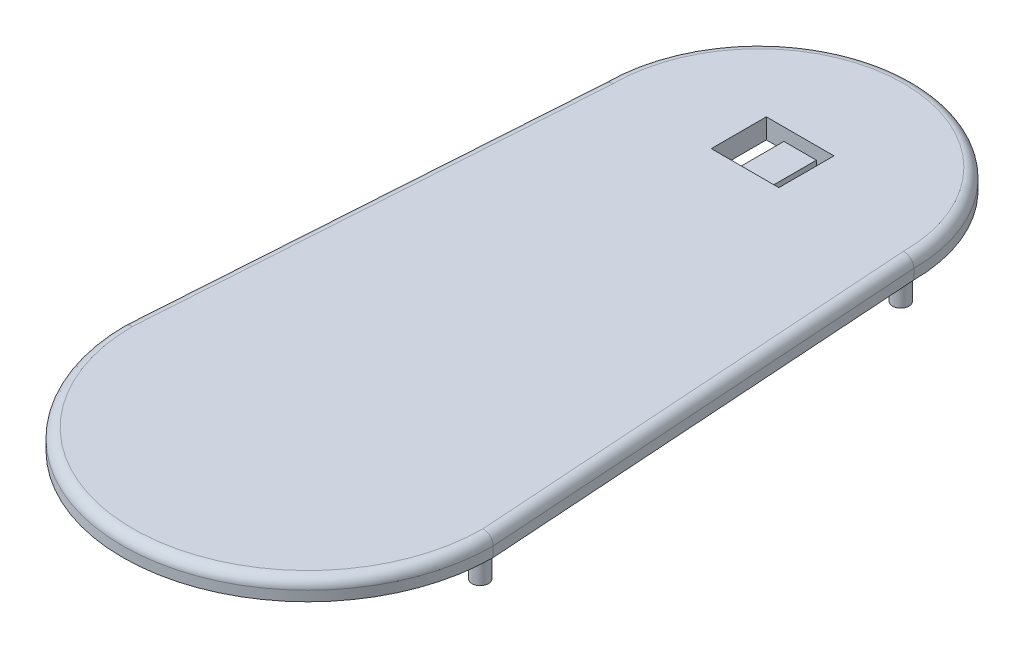
SolidWorks part; units mm, degrees
ref_plane "Front Plane" through (0, 0, 0) normal (0, 0, 1) x (1, 0, 0)
ref_plane "Top Plane" through (0, 0, 0) normal (0, 1, 0) x (1, 0, 0)
ref_plane "Right Plane" through (0, 0, 0) normal (1, 0, 0) x (0, 0, -1)
sketch "Sketch1" plane through (0, 0, 0) normal (0, 1, 0) x (1, 0, 0)
  line L0 (-31, 45) -> (-37, -45)
  line L1 (-31, 45) -> (31, 45)
  line L2 (-31, 45) -> (-31, -45)
  line L3 (-31, -45) -> (31, -45)
  line L4 (31, 45) -> (31, -45)
  line L5 (-31, 45) -> (31, -45) construction
  line L6 (-31, -45) -> (31, 45) construction
  line L7 (31, 45) -> (37, -45)
  circle A0 centre (0, 45) radius 31
  circle A1 centre (0, -45) radius 37
  point P0 (0, 0)
  dimension "D3" = 74
  dimension "D1" = 62
  dimension "D2" = 90
extrude "Boss-Extrude4" add sketch "Sketch1" along normal blind 4 contours L7 A1 L4 L3 L2 L0 | L4 A1 L2 L3 | A1 L4 A0 L2 | L1 A0 | L1 A0 | A1 L7 L4 | A1 L2 L0 region at (-32.823, 0, 5.2761) region at (0, 0, -58.1568) region at (0, 0, -4.2186) region at (0, 0, -31.8432) region at (0, 0, 59.0475) region at (32.823, 0, 5.2761) region at (0, 0, 28.6312)
sketch "Sketch8" plane through (0, 0, 0) normal (0, -1, 0) x (1, 0, 0)
  circle A0 centre (-34.4, 45) radius 1.65
  circle A1 centre (34.4, 45) radius 1.65
  circle A2 centre (28.4, -45) radius 1.65
  circle A3 centre (-28.4, -45) radius 1.65
  dimension "D1" = 3.3
  dimension "D3" = 3.3
  dimension "D5" = 3.3
  dimension "D7" = 3.3
  dimension "D2" = 2.6
  dimension "D4" = 2.6
  dimension "D6" = 2.6
  dimension "D8" = 2.6
extrude "Boss-Extrude5" add sketch "Sketch8" along normal blind 5
sketch "Sketch9" plane through (0, 4, 0) normal (0, 1, 0) x (1, 0, 0)
  line L1 (-7.9566, 54.5082) -> (5.5434, 54.5082)
  line L2 (-7.9566, 54.5082) -> (-7.9566, 43.5082)
  line L3 (-7.9566, 43.5082) -> (5.5434, 43.5082)
  line L4 (5.5434, 54.5082) -> (5.5434, 43.5082)
  line L5 (-7.9566, 54.5082) -> (5.5434, 43.5082) construction
  line L6 (-7.9566, 43.5082) -> (5.5434, 54.5082) construction
  point P0 (-1.2066, 49.0082)
  dimension "D1" = 13.5
  dimension "D2" = 11
extrude "Cut-Extrude3" cut sketch "Sketch9" against normal blind 2.5
sketch "Sketch10" plane through (0, 1.5, 0) normal (0, 1, 0) x (1, 0, 0)
  line L0 (-7.9566, 43.5082) -> (5.5434, 43.5082) construction
  line L1 (-7.9566, 54.5082) -> (-4.4566, 54.5082)
  line L2 (-7.9566, 54.5082) -> (-7.9566, 43.5082)
  line L3 (-7.9566, 43.5082) -> (-4.4566, 43.5082)
  line L4 (-4.4566, 54.5082) -> (-4.4566, 43.5082)
  line L6 (5.5434, 54.5082) -> (2.0434, 54.5082)
  line L7 (5.5434, 54.5082) -> (5.5434, 43.5082)
  line L8 (5.5434, 43.5082) -> (2.0434, 43.5082)
  line L9 (2.0434, 54.5082) -> (2.0434, 43.5082)
  dimension "D1" = 3.5
  dimension "D2" = 3.5
extrude "Cut-Extrude4" cut sketch "Sketch10" against normal blind 8.5
fillet "Fillet1" radius 2 4 edges at (0, 4, -76) (34, 4, 0) (0, 4, 82) (-34, 4, 0)
